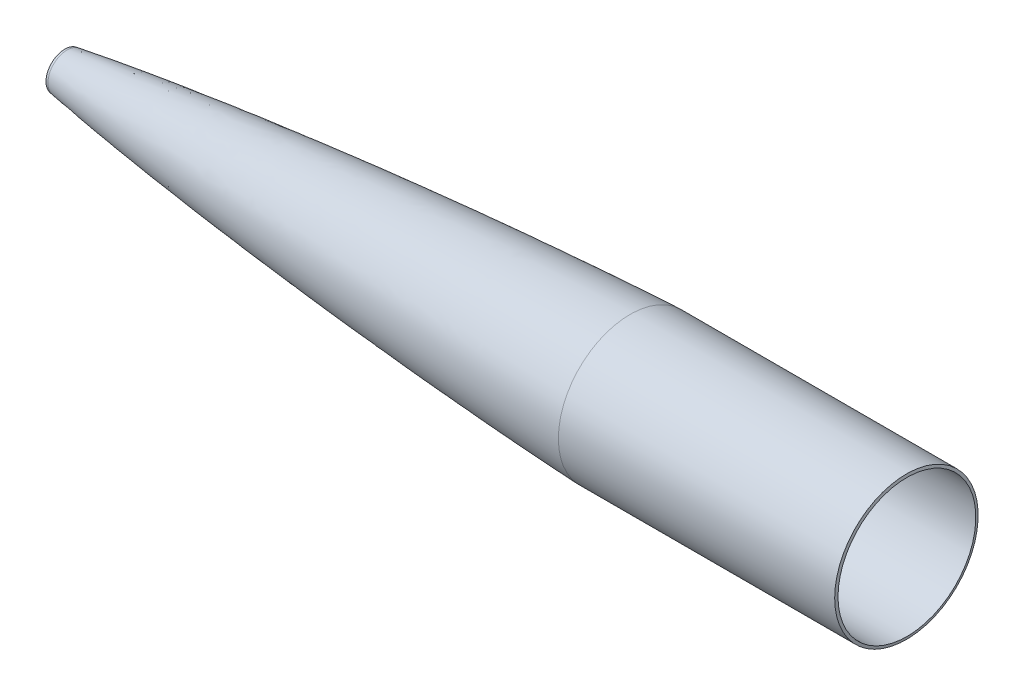
SolidWorks part; units mm, degrees
ref_plane "Front" through (0, 0, 0) normal (0, 0, 1) x (1, 0, 0)
ref_plane "Top" through (0, 0, 0) normal (0, 1, 0) x (1, 0, 0)
ref_plane "Right" through (0, 0, 0) normal (1, 0, 0) x (0, 0, -1)
other "von Karman body"
sketch "Sketch1" plane through (0, 0, 0) normal (0, 1, 0) x (1, 0, 0)
  line L0 (838.2, 83.82) -> (1041.4, 83.82) construction
  line L1 (1041.9598, 80.645) -> (1055.402, 4.4107) construction
  line L2 (98.2259, 21.4654) -> (95.6842, 21.058)
  line L3 (96.6803, 12.7) -> (83.9803, 12.7) construction
  line L4 (96.6803, 12.7) -> (98.2259, 21.4654) construction
  line L5 (83.9803, 12.7) -> (80.7329, 4.8601) construction
  line L6 (0, 0) -> (1055.7879, 0) construction
  line L7 (83.9803, 12.7) -> (82.9291, 18.9624) construction
  line L8 (79.7661, 0) -> (79.7661, 6.839) construction
  line L9 (1042.5197, 77.47) -> (731.3785, 77.47)
  line L10 (98.7269, 18.3302) -> (98.7269, 0)
  line L11 (95.6842, 0) -> (95.6842, 21.058)
  line L12 (1042.5197, 80.645) -> (731.3084, 80.645) construction
  line L13 (95.6842, 0) -> (98.7269, 0)
  line L14 (1042.5197, 77.47) -> (1041.9598, 80.645)
  line L21 (1041.9598, 80.645) -> (731.3084, 80.645)
  circle A0 centre (3.2859, 0) radius 1.5875 construction
  arc A1 (80.7329, 4.8601) -> (79.7661, 0) centre (92.4661, 0) ccw construction
  arc A2 (1055.402, 4.4107) -> (1055.7879, 0) centre (1030.3879, 0) cw construction
  spline S0 degree 1 poles (98.2259, 21.4654) (731.3084, 80.645) knots 0 0 1 1 construction
  spline S1 degree 3 poles (98.2259, 21.4654) (124.3977, 25.6479) (176.8847, 33.1097) (282.1195, 46.0132) (413.9798, 59.3568) (572.5069, 72.0563) (678.3519, 78.3063) (731.3084, 80.645) knots 0.119456 0.119456 0.119456 0.119456 0.213683 0.307909 0.496362 0.684815 0.873268 0.873268 0.873268 0.873268
  spline S2 degree 4 poles (0, 0) (0.003, 0.0082) (0.0102, 0.024) (0.03, 0.0526) (0.0649, 0.0913) (0.1084, 0.1337) (0.1742, 0.1902) (0.2565, 0.254) (0.4287, 0.3755) (0.6477, 0.5094) (0.8967, 0.6483) (1.1954, 0.8025) (1.4629, 0.9334) (1.9041, 1.1393) (2.6896, 1.4796) (4.1163, 2.0409) (6.8305, 2.9882) (11.8188, 4.5114) (21.1813, 6.9846) (37.5193, 10.6856) (65.2772, 16.0943) (103.3896, 22.4744) (149.5855, 29.2908) (200.9592, 36.0811) (252.4063, 42.285) (303.9097, 48.0016) (355.4582, 53.2943) (407.0449, 58.2003) (458.6648, 62.7429) (510.3146, 66.9331) (561.9916, 70.772) (613.6942, 74.2501) (665.4211, 77.3457) (710.703, 79.6843) (749.5307, 81.3797) (780.8418, 82.5024) (801.92, 83.1162) (819.2363, 83.5008) (830.0782, 83.6603) (835.4995, 83.711) (838.2103, 83.7174) knots 0 0 0 0 0 0.000041 0.000082 0.000164 0.000247 0.000329 0.000493 0.000658 0.001245 0.001545 0.001844 0.002251 0.002657 0.003853 0.005902 0.009516 0.016281 0.028569 0.051794 0.088907 0.150314 0.211721 0.273128 0.334535 0.395942 0.457348 0.518755 0.580162 0.641569 0.702976 0.764383 0.825789 0.887196 0.9179 0.948603 0.974302 0.987151 1 1 1 1 1 construction
  spline S3 degree 4 poles (0, 0) (0.003, 0.0082) (0.0102, 0.024) (0.03, 0.0526) (0.0649, 0.0913) (0.1084, 0.1337) (0.1742, 0.1902) (0.2565, 0.254) (0.4287, 0.3755) (0.6477, 0.5094) (0.8967, 0.6483) (1.1954, 0.8025) (1.4629, 0.9334) (1.9041, 1.1393) (2.6896, 1.4796) (4.1163, 2.0409) (6.8305, 2.9882) (11.8188, 4.5114) (21.1813, 6.9846) (37.5193, 10.6856) (58.2545, 14.7259) (76.5078, 17.9206) (89.9571, 20.1364) (95.6842, 21.058) knots 0 0 0 0 0 0.000041 0.000082 0.000164 0.000247 0.000329 0.000493 0.000658 0.001245 0.001545 0.001844 0.002251 0.002657 0.003853 0.005902 0.009516 0.016281 0.028569 0.051794 0.088907 0.116404 0.116404 0.116404 0.116404 0.116404 construction
  spline S5 degree 3 poles (98.7269, 18.3302) (113.9949, 20.7701) (144.5778, 25.3307) (205.8981, 33.5898) (282.7202, 42.6805) (375.074, 52.1768) (467.5477, 60.4692) (560.1163, 67.6374) (637.3228, 72.6533) (694.4209, 75.7531) (720.626, 76.9951) (731.3785, 77.47) knots 0.119456 0.119456 0.119456 0.119456 0.17449 0.229524 0.339592 0.44966 0.559728 0.669796 0.779864 0.834898 0.873185 0.873185 0.873185 0.873185
  point P5 (0, 0)
  dimension "D6" = 3.175
  dimension "D9" = 25.4
  dimension "D10" = 12.7
  dimension "D1" = 12.7
  dimension "D2" = 100
  dimension "D3" = 203.2
  dimension "D4" = 6.35
  dimension "D5" = 838.2
  dimension "D7" = 67.5
  dimension "D8" = 80
  dimension "D11" = 83.82
  dimension "D12" = 12.7
revolve "Revolve5" add sketch "Sketch1" angle 360 about L6
chamfer "Chamfer1" distance 16.51 angle 45 1 edges at (98.7269, 0, 18.3302) first distance on face at (98.7269, 0, 18.3302)
sketch "Sketch2" plane through (95.6842, 0, 0) normal (-1, 0, 0) x (0, 0, 1)
  circle A0 centre (0, 0) radius 12.25
extrude "Cut-Extrude1" cut sketch "Sketch2" against normal blind 165
scale "Scale1" [suppressed]
